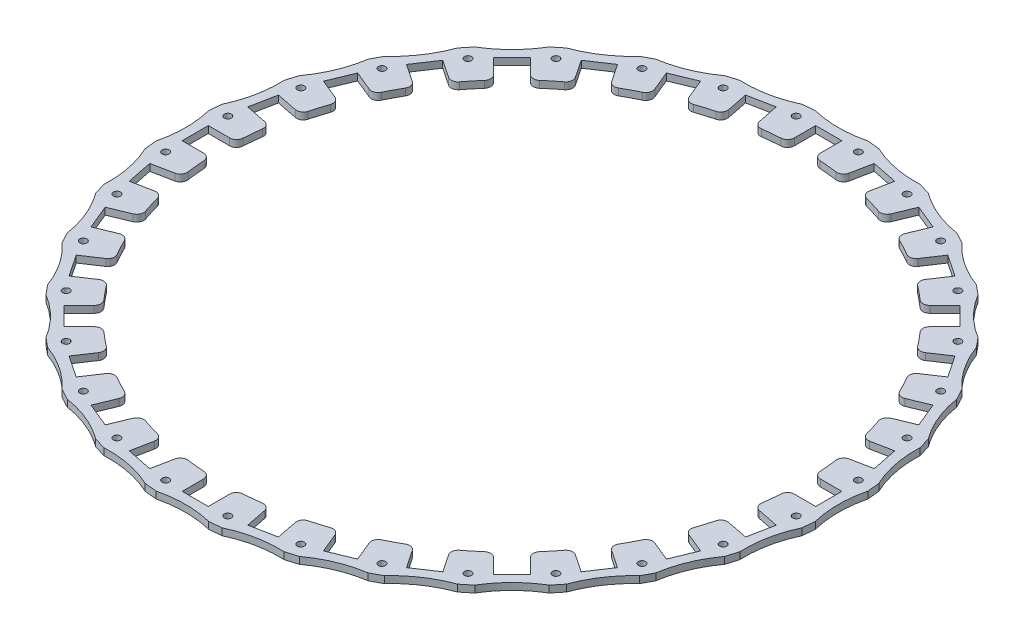
SolidWorks part; units mm, degrees
ref_plane "Front" through (0, 0, 0) normal (0, 0, 1) x (1, 0, 0)
ref_plane "Top" through (0, 0, 0) normal (0, 1, 0) x (1, 0, 0)
ref_plane "Right" through (0, 0, 0) normal (1, 0, 0) x (0, 0, -1)
sketch "Sketch1" plane through (0, 0, 0) normal (0, 1, 0) x (1, 0, 0)
  line L0 (133.35, 0) -> (146.05, 0) construction
  line L1 (136.2142, 6.0325) -> (146.05, 6.0325)
  line L2 (134.7737, -20.6575) -> (144.4206, -22.5764)
  line L3 (136.2142, -6.0325) -> (146.05, -6.0325)
  line L4 (146.05, 6.0325) -> (146.05, -6.0325)
  line L5 (133.35, 0) -> (146.05, -6.0325) construction
  line L6 (133.35, 0) -> (146.05, 6.0325) construction
  line L7 (144.4206, -22.5764) -> (142.0668, -34.4095)
  line L8 (132.42, -32.4907) -> (142.0668, -34.4095)
  line L9 (128.154, -46.5536) -> (137.2411, -50.3176)
  line L10 (137.2411, -50.3176) -> (132.6241, -61.4642)
  line L11 (123.5369, -57.7002) -> (132.6241, -61.4642)
  line L12 (116.6094, -70.6607) -> (124.7876, -76.1252)
  line L13 (124.7876, -76.1252) -> (118.0847, -86.1569)
  line L14 (109.9065, -80.6924) -> (118.0847, -86.1569)
  line L15 (100.5836, -92.0523) -> (107.5386, -99.0073)
  line L16 (107.5386, -99.0073) -> (99.0073, -107.5386)
  line L17 (92.0523, -100.5836) -> (99.0073, -107.5386)
  line L18 (80.6924, -109.9065) -> (86.1569, -118.0847)
  line L19 (86.1569, -118.0847) -> (76.1252, -124.7876)
  line L20 (70.6607, -116.6094) -> (76.1252, -124.7876)
  line L21 (57.7002, -123.5369) -> (61.4642, -132.6241)
  line L22 (61.4642, -132.6241) -> (50.3176, -137.2411)
  line L23 (46.5536, -128.154) -> (50.3176, -137.2411)
  line L24 (32.4907, -132.42) -> (34.4095, -142.0668)
  line L25 (34.4095, -142.0668) -> (22.5764, -144.4206)
  line L26 (20.6575, -134.7737) -> (22.5764, -144.4206)
  line L27 (6.0325, -136.2142) -> (6.0325, -146.05)
  line L28 (6.0325, -146.05) -> (-6.0325, -146.05)
  line L29 (-6.0325, -136.2142) -> (-6.0325, -146.05)
  line L30 (-20.6575, -134.7737) -> (-22.5764, -144.4206)
  line L31 (-22.5764, -144.4206) -> (-34.4095, -142.0668)
  line L32 (-32.4907, -132.42) -> (-34.4095, -142.0668)
  line L33 (-46.5536, -128.154) -> (-50.3176, -137.2411)
  line L34 (-50.3176, -137.2411) -> (-61.4642, -132.6241)
  line L35 (-57.7002, -123.5369) -> (-61.4642, -132.6241)
  line L36 (-70.6607, -116.6094) -> (-76.1252, -124.7876)
  line L37 (-76.1252, -124.7876) -> (-86.1569, -118.0847)
  line L38 (-80.6924, -109.9065) -> (-86.1569, -118.0847)
  line L39 (-92.0523, -100.5836) -> (-99.0073, -107.5386)
  line L40 (-99.0073, -107.5386) -> (-107.5386, -99.0073)
  line L41 (-100.5836, -92.0523) -> (-107.5386, -99.0073)
  line L42 (-109.9065, -80.6924) -> (-118.0847, -86.1569)
  line L43 (-118.0847, -86.1569) -> (-124.7876, -76.1252)
  line L44 (-116.6094, -70.6607) -> (-124.7876, -76.1252)
  line L45 (-123.5369, -57.7002) -> (-132.6241, -61.4642)
  line L46 (-132.6241, -61.4642) -> (-137.2411, -50.3176)
  line L47 (-128.154, -46.5536) -> (-137.2411, -50.3176)
  line L48 (-132.42, -32.4907) -> (-142.0668, -34.4095)
  line L49 (-142.0668, -34.4095) -> (-144.4206, -22.5764)
  line L50 (-134.7737, -20.6575) -> (-144.4206, -22.5764)
  line L51 (-136.2142, -6.0325) -> (-146.05, -6.0325)
  line L52 (-146.05, -6.0325) -> (-146.05, 6.0325)
  line L53 (-136.2142, 6.0325) -> (-146.05, 6.0325)
  line L54 (-134.7737, 20.6575) -> (-144.4206, 22.5764)
  line L55 (-144.4206, 22.5764) -> (-142.0668, 34.4095)
  line L56 (-132.42, 32.4907) -> (-142.0668, 34.4095)
  line L57 (-128.154, 46.5536) -> (-137.2411, 50.3176)
  line L58 (-137.2411, 50.3176) -> (-132.6241, 61.4642)
  line L59 (-123.5369, 57.7002) -> (-132.6241, 61.4642)
  line L60 (-116.6094, 70.6607) -> (-124.7876, 76.1252)
  line L61 (-124.7876, 76.1252) -> (-118.0847, 86.1569)
  line L62 (-109.9065, 80.6924) -> (-118.0847, 86.1569)
  line L63 (-100.5836, 92.0523) -> (-107.5386, 99.0073)
  line L64 (-107.5386, 99.0073) -> (-99.0073, 107.5386)
  line L65 (-92.0523, 100.5836) -> (-99.0073, 107.5386)
  line L66 (-80.6924, 109.9065) -> (-86.1569, 118.0847)
  line L67 (-86.1569, 118.0847) -> (-76.1252, 124.7876)
  line L68 (-70.6607, 116.6094) -> (-76.1252, 124.7876)
  line L69 (-57.7002, 123.5369) -> (-61.4642, 132.6241)
  line L70 (-61.4642, 132.6241) -> (-50.3176, 137.2411)
  line L71 (-46.5536, 128.154) -> (-50.3176, 137.2411)
  line L72 (-32.4907, 132.42) -> (-34.4095, 142.0668)
  line L73 (-34.4095, 142.0668) -> (-22.5764, 144.4206)
  line L74 (-20.6575, 134.7737) -> (-22.5764, 144.4206)
  line L75 (-6.0325, 136.2142) -> (-6.0325, 146.05)
  line L76 (-6.0325, 146.05) -> (6.0325, 146.05)
  line L77 (6.0325, 136.2142) -> (6.0325, 146.05)
  line L78 (20.6575, 134.7737) -> (22.5764, 144.4206)
  line L79 (22.5764, 144.4206) -> (34.4095, 142.0668)
  line L80 (32.4907, 132.42) -> (34.4095, 142.0668)
  line L81 (46.5536, 128.154) -> (50.3176, 137.2411)
  line L82 (50.3176, 137.2411) -> (61.4642, 132.6241)
  line L83 (57.7002, 123.5369) -> (61.4642, 132.6241)
  line L84 (70.6607, 116.6094) -> (76.1252, 124.7876)
  line L85 (76.1252, 124.7876) -> (86.1569, 118.0847)
  line L86 (80.6924, 109.9065) -> (86.1569, 118.0847)
  line L87 (92.0523, 100.5836) -> (99.0073, 107.5386)
  line L88 (99.0073, 107.5386) -> (107.5386, 99.0073)
  line L89 (100.5836, 92.0523) -> (107.5386, 99.0073)
  line L90 (109.9065, 80.6924) -> (118.0847, 86.1569)
  line L91 (118.0847, 86.1569) -> (124.7876, 76.1252)
  line L92 (116.6094, 70.6607) -> (124.7876, 76.1252)
  line L93 (123.5369, 57.7002) -> (132.6241, 61.4642)
  line L94 (132.6241, 61.4642) -> (137.2411, 50.3176)
  line L95 (128.154, 46.5536) -> (137.2411, 50.3176)
  line L96 (132.42, 32.4907) -> (142.0668, 34.4095)
  line L97 (142.0668, 34.4095) -> (144.4206, 22.5764)
  line L98 (134.7737, 20.6575) -> (144.4206, 22.5764)
  circle A0 centre (0, 0) radius 152.4
  arc A1 (133.0464, 8.9934) -> (133.0464, -8.9934) centre (0, 0) ccw
  arc A2 (151.9186, 12.1031) -> (151.9186, -12.1031) centre (201.2558, 0) ccw
  arc A3 (151.3608, -17.7673) -> (146.6384, -41.5084) centre (197.3887, -39.2631) ccw
  arc A4 (144.9862, -46.9549) -> (135.7229, -69.3186) centre (185.9361, -77.0173) ccw
  arc A5 (133.0399, -74.3381) -> (119.5916, -94.4648) centre (167.3381, -111.8117) ccw
  arc A6 (115.9809, -98.8645) -> (98.8645, -115.9809) centre (142.3093, -142.3093) ccw
  arc A7 (94.4648, -119.5916) -> (74.3381, -133.0399) centre (111.8117, -167.3381) ccw
  arc A8 (69.3186, -135.7229) -> (46.9549, -144.9862) centre (77.0173, -185.9361) ccw
  arc A9 (41.5084, -146.6384) -> (17.7673, -151.3608) centre (39.2631, -197.3887) ccw
  arc A10 (12.1031, -151.9186) -> (-12.1031, -151.9186) centre (0, -201.2558) ccw
  arc A11 (-17.7673, -151.3608) -> (-41.5084, -146.6384) centre (-39.2631, -197.3887) ccw
  arc A12 (-46.9549, -144.9862) -> (-69.3186, -135.7229) centre (-77.0173, -185.9361) ccw
  arc A13 (-74.3381, -133.0399) -> (-94.4648, -119.5916) centre (-111.8117, -167.3381) ccw
  arc A14 (-98.8645, -115.9809) -> (-115.9809, -98.8645) centre (-142.3093, -142.3093) ccw
  arc A15 (-119.5916, -94.4648) -> (-133.0399, -74.3381) centre (-167.3381, -111.8117) ccw
  arc A16 (-135.7229, -69.3186) -> (-144.9862, -46.9549) centre (-185.9361, -77.0173) ccw
  arc A17 (-146.6384, -41.5084) -> (-151.3608, -17.7673) centre (-197.3887, -39.2631) ccw
  arc A18 (-151.9186, -12.1031) -> (-151.9186, 12.1031) centre (-201.2558, 0) ccw
  arc A19 (-151.3608, 17.7673) -> (-146.6384, 41.5084) centre (-197.3887, 39.2631) ccw
  arc A20 (-144.9862, 46.9549) -> (-135.7229, 69.3186) centre (-185.9361, 77.0173) ccw
  arc A21 (-133.0399, 74.3381) -> (-119.5916, 94.4648) centre (-167.3381, 111.8117) ccw
  arc A22 (-115.9809, 98.8645) -> (-98.8645, 115.9809) centre (-142.3093, 142.3093) ccw
  arc A23 (-94.4648, 119.5916) -> (-74.3381, 133.0399) centre (-111.8117, 167.3381) ccw
  arc A24 (-69.3186, 135.7229) -> (-46.9549, 144.9862) centre (-77.0173, 185.9361) ccw
  arc A25 (-41.5084, 146.6384) -> (-17.7673, 151.3608) centre (-39.2631, 197.3887) ccw
  arc A26 (-12.1031, 151.9186) -> (12.1031, 151.9186) centre (0, 201.2558) ccw
  arc A27 (17.7673, 151.3608) -> (41.5084, 146.6384) centre (39.2631, 197.3887) ccw
  arc A28 (46.9549, 144.9862) -> (69.3186, 135.7229) centre (77.0173, 185.9361) ccw
  arc A29 (74.3381, 133.0399) -> (94.4648, 119.5916) centre (111.8117, 167.3381) ccw
  arc A30 (98.8645, 115.9809) -> (115.9809, 98.8645) centre (142.3093, 142.3093) ccw
  arc A31 (119.5916, 94.4648) -> (133.0399, 74.3381) centre (167.3381, 111.8117) ccw
  arc A32 (135.7229, 69.3186) -> (144.9862, 46.9549) centre (185.9361, 77.0173) ccw
  arc A33 (146.6384, 41.5084) -> (151.3608, 17.7673) centre (197.3887, 39.2631) ccw
  arc A34 (136.2142, 6.0325) -> (133.0464, 8.9934) centre (136.2142, 9.2075) cw
  arc A35 (136.2142, -6.0325) -> (133.0464, -8.9934) centre (136.2142, -9.2075) ccw
  arc A36 (134.7737, -20.6575) -> (132.2445, -17.1355) centre (135.3931, -17.5435) cw
  arc A37 (132.42, -32.4907) -> (128.7354, -34.7766) centre (131.8005, -35.6046) ccw
  arc A38 (128.154, -46.5536) -> (126.3605, -42.6059) centre (129.369, -43.6203) cw
  arc A39 (123.5369, -57.7002) -> (119.4772, -59.2234) centre (122.3219, -60.6335) ccw
  arc A40 (116.6094, -70.6607) -> (115.6205, -66.4389) centre (118.3733, -68.0208) cw
  arc A41 (109.9065, -80.6924) -> (105.6276, -81.3943) centre (108.1425, -83.3323) ccw
  arc A42 (100.5836, -92.0523) -> (100.4373, -87.7187) centre (102.8286, -89.8073) cw
  arc A43 (92.0523, -100.5836) -> (87.7187, -100.4373) centre (89.8073, -102.8286) ccw
  arc A44 (80.6924, -109.9065) -> (81.3943, -105.6276) centre (83.3323, -108.1425) cw
  arc A45 (70.6607, -116.6094) -> (66.4389, -115.6205) centre (68.0208, -118.3733) ccw
  arc A46 (57.7002, -123.5369) -> (59.2234, -119.4772) centre (60.6335, -122.3219) cw
  arc A47 (46.5536, -128.154) -> (42.6059, -126.3605) centre (43.6203, -129.369) ccw
  arc A48 (32.4907, -132.42) -> (34.7766, -128.7354) centre (35.6046, -131.8005) cw
  arc A49 (20.6575, -134.7737) -> (17.1355, -132.2445) centre (17.5435, -135.3931) ccw
  arc A50 (6.0325, -136.2142) -> (8.9934, -133.0464) centre (9.2075, -136.2142) cw
  arc A51 (-6.0325, -136.2142) -> (-8.9934, -133.0464) centre (-9.2075, -136.2142) ccw
  arc A52 (-20.6575, -134.7737) -> (-17.1355, -132.2445) centre (-17.5435, -135.3931) cw
  arc A53 (-32.4907, -132.42) -> (-34.7766, -128.7354) centre (-35.6046, -131.8005) ccw
  arc A54 (-46.5536, -128.154) -> (-42.6059, -126.3605) centre (-43.6203, -129.369) cw
  arc A55 (-57.7002, -123.5369) -> (-59.2234, -119.4772) centre (-60.6335, -122.3219) ccw
  arc A56 (-70.6607, -116.6094) -> (-66.4389, -115.6205) centre (-68.0208, -118.3733) cw
  arc A57 (-80.6924, -109.9065) -> (-81.3943, -105.6276) centre (-83.3323, -108.1425) ccw
  arc A58 (-92.0523, -100.5836) -> (-87.7187, -100.4373) centre (-89.8073, -102.8286) cw
  arc A59 (-100.5836, -92.0523) -> (-100.4373, -87.7187) centre (-102.8286, -89.8073) ccw
  arc A60 (-109.9065, -80.6924) -> (-105.6276, -81.3943) centre (-108.1425, -83.3323) cw
  arc A61 (-116.6094, -70.6607) -> (-115.6205, -66.4389) centre (-118.3733, -68.0208) ccw
  arc A62 (-123.5369, -57.7002) -> (-119.4772, -59.2234) centre (-122.3219, -60.6335) cw
  arc A63 (-128.154, -46.5536) -> (-126.3605, -42.6059) centre (-129.369, -43.6203) ccw
  arc A64 (-132.42, -32.4907) -> (-128.7354, -34.7766) centre (-131.8005, -35.6046) cw
  arc A65 (-134.7737, -20.6575) -> (-132.2445, -17.1355) centre (-135.3931, -17.5435) ccw
  arc A66 (-136.2142, -6.0325) -> (-133.0464, -8.9934) centre (-136.2142, -9.2075) cw
  arc A67 (-136.2142, 6.0325) -> (-133.0464, 8.9934) centre (-136.2142, 9.2075) ccw
  arc A68 (-134.7737, 20.6575) -> (-132.2445, 17.1355) centre (-135.3931, 17.5435) cw
  arc A69 (-132.42, 32.4907) -> (-128.7354, 34.7766) centre (-131.8005, 35.6046) ccw
  arc A70 (-128.154, 46.5536) -> (-126.3605, 42.6059) centre (-129.369, 43.6203) cw
  arc A71 (-123.5369, 57.7002) -> (-119.4772, 59.2234) centre (-122.3219, 60.6335) ccw
  arc A72 (-116.6094, 70.6607) -> (-115.6205, 66.4389) centre (-118.3733, 68.0208) cw
  arc A73 (-109.9065, 80.6924) -> (-105.6276, 81.3943) centre (-108.1425, 83.3323) ccw
  arc A74 (-100.5836, 92.0523) -> (-100.4373, 87.7187) centre (-102.8286, 89.8073) cw
  arc A75 (-92.0523, 100.5836) -> (-87.7187, 100.4373) centre (-89.8073, 102.8286) ccw
  arc A76 (-80.6924, 109.9065) -> (-81.3943, 105.6276) centre (-83.3323, 108.1425) cw
  arc A77 (-70.6607, 116.6094) -> (-66.4389, 115.6205) centre (-68.0208, 118.3733) ccw
  arc A78 (-57.7002, 123.5369) -> (-59.2234, 119.4772) centre (-60.6335, 122.3219) cw
  arc A79 (-46.5536, 128.154) -> (-42.6059, 126.3605) centre (-43.6203, 129.369) ccw
  arc A80 (-32.4907, 132.42) -> (-34.7766, 128.7354) centre (-35.6046, 131.8005) cw
  arc A81 (-20.6575, 134.7737) -> (-17.1355, 132.2445) centre (-17.5435, 135.3931) ccw
  arc A82 (-6.0325, 136.2142) -> (-8.9934, 133.0464) centre (-9.2075, 136.2142) cw
  arc A83 (6.0325, 136.2142) -> (8.9934, 133.0464) centre (9.2075, 136.2142) ccw
  arc A84 (20.6575, 134.7737) -> (17.1355, 132.2445) centre (17.5435, 135.3931) cw
  arc A85 (32.4907, 132.42) -> (34.7766, 128.7354) centre (35.6046, 131.8005) ccw
  arc A86 (46.5536, 128.154) -> (42.6059, 126.3605) centre (43.6203, 129.369) cw
  arc A87 (57.7002, 123.5369) -> (59.2234, 119.4772) centre (60.6335, 122.3219) ccw
  arc A88 (70.6607, 116.6094) -> (66.4389, 115.6205) centre (68.0208, 118.3733) cw
  arc A89 (80.6924, 109.9065) -> (81.3943, 105.6276) centre (83.3323, 108.1425) ccw
  arc A90 (92.0523, 100.5836) -> (87.7187, 100.4373) centre (89.8073, 102.8286) cw
  arc A91 (100.5836, 92.0523) -> (100.4373, 87.7187) centre (102.8286, 89.8073) ccw
  arc A92 (109.9065, 80.6924) -> (105.6276, 81.3943) centre (108.1425, 83.3323) cw
  arc A93 (116.6094, 70.6607) -> (115.6205, 66.4389) centre (118.3733, 68.0208) ccw
  arc A94 (123.5369, 57.7002) -> (119.4772, 59.2234) centre (122.3219, 60.6335) cw
  arc A95 (128.154, 46.5536) -> (126.3605, 42.6059) centre (129.369, 43.6203) ccw
  arc A96 (132.42, 32.4907) -> (128.7354, 34.7766) centre (131.8005, 35.6046) cw
  arc A97 (134.7737, 20.6575) -> (132.2445, 17.1355) centre (135.3931, 17.5435) ccw
  point P4 (133.35, 0)
  point P231 (0, 0)
  point P328 (0, 0)
  point P363 (0, 0)
  dimension "D1" = 304.8
  dimension "D2" = 19.05
  dimension "D3" = 12.065
  dimension "D6" = 50.8
  dimension "D5" = 3.175
  dimension "D4" = 12.7
  dimension "D7" = 24.2062
  dimension "D8" = 5.6916
extrude "Boss-Extrude1" add sketch "Sketch1" along normal blind 3.175 contours A0 A1 L31 L34 L52 region at (146.1589, 0, 0)
ref_axis "Axis1" through (0, 50, 0) along (0, -1, 0)
sketch "Sketch4" plane through (0, 3.175, 0) normal (0, 1, 0) x (1, 0, 0)
  line L0 (0, 0) -> (132.7079, 13.0706) construction
  circle A0 centre (145.3467, 14.3154) radius 1.6383
  circle A2 centre (0, 0) radius 146.05 construction
  arc A3 (133.0464, 8.9934) -> (132.2445, 17.1355) centre (0, 0) ccw construction
  dimension "D1" = 292.1
  dimension "D2" = 3.2766
extrude "Cut-Extrude1" cut sketch "Sketch4" against normal through all
pattern_circular "CirPattern1" count 32 over 360 about axis through (0, 50, 0) along (0, -1, 0) of "Cut-Extrude1"
